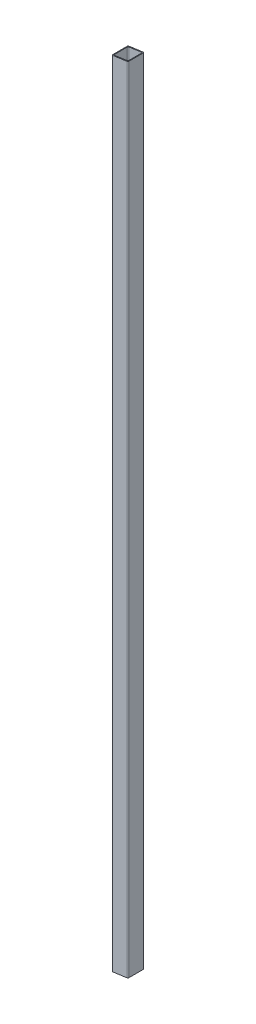
SolidWorks part; units mm, degrees
ref_plane "Front Plane" through (0, 0, 0) normal (0, 0, 1) x (1, 0, 0)
ref_plane "Top Plane" through (0, 0, 0) normal (0, 1, 0) x (1, 0, 0)
ref_plane "Right Plane" through (0, 0, 0) normal (1, 0, 0) x (0, 0, -1)
sketch "Sketch1" plane through (0, 0, 0) normal (0, 1, 0) x (1, 0, 0)
  line L1 (5, 0) -> (95, 0)
  line L2 (0, -5) -> (0, -95)
  line L3 (5, -100) -> (95, -100)
  line L4 (100, -5) -> (100, -95)
  line L5 (10, -5) -> (90, -5)
  line L6 (5, -10) -> (5, -90)
  line L7 (10, -95) -> (90, -95)
  line L8 (95, -10) -> (95, -90)
  arc A0 (10, -95) -> (5, -90) centre (10, -90) cw
  arc A1 (10, -5) -> (5, -10) centre (10, -10) ccw
  arc A2 (100, -5) -> (95, 0) centre (95, -5) ccw
  arc A3 (100, -95) -> (95, -100) centre (95, -95) cw
  arc A4 (5, -100) -> (0, -95) centre (5, -95) cw
  arc A5 (5, 0) -> (0, -5) centre (5, -5) ccw
  arc A6 (95, -90) -> (90, -95) centre (90, -90) cw
  arc A7 (90, -5) -> (95, -10) centre (90, -10) cw
  point P9 (50, -95)
  point P16 (100, 0)
  point P21 (0, -100)
  point P24 (0, 0)
  dimension "D7" = 5
  dimension "D8" = 5
  dimension "D1" = 100
  dimension "D2" = 100
  dimension "D3" = 5
  dimension "D4" = 5
  dimension "D5" = 5
  dimension "D6" = 5
extrude "Boss-Extrude1" add sketch "Sketch1" along normal blind 4950
sketch "Sketch2" plane through (0, 0, 0) normal (0, 0, -1) x (-1, 0, 0)
  line L1 (-100, 14.0541) -> (0, 0)
  line L2 (0, 0) -> (-100, 0)
  line L3 (-100, 0) -> (-100, 14.0541)
  line L4 (-238.7113, 500) -> (182.2276, 500) construction
  line L5 (-100, 4950) -> (0, 4935.9459)
  line L6 (-100, 4935.9459) -> (-100, 4950)
  line L7 (-100, 4935.9459) -> (0, 4935.9459)
  line L8 (-100, 4950) -> (0, 4950)
  line L9 (0, 4950) -> (0, 4935.9459)
  line M5 (-5, 0) -> (-5, 4950)
  line M6 (-5, 4950) -> (-95, 4950)
  line M7 (-95, 4950) -> (-95, 0)
  dimension "D1" = 100
  dimension "D2" = 8
  dimension "D3" = 0
  dimension "D4" = 500
  dimension "D5" = 4950
  dimension "D6" = 100
  dimension "D7" = 100
  dimension "D8" = 8
  dimension "D9" = 100
extrude "Cut-Extrude1" cut sketch "Sketch2" against normal blind 1000 contours L5 M7 M5 M6 | L9 L8 L5 M5 | L8 L5 M7 | L3 L1 L2 region at (36.5, 4945.5378, 0) region at (96.6667, 4949.7658, 0) region at (2.4786, 4943.1471, 0)
